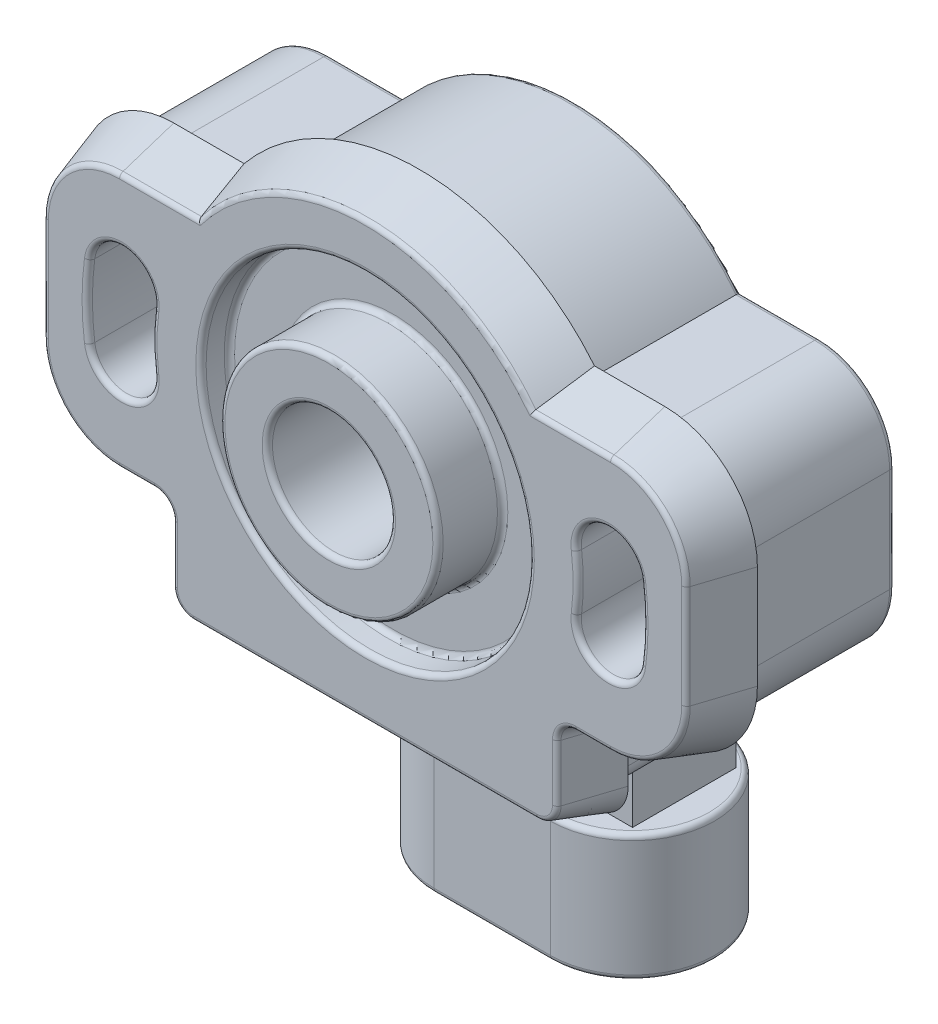
SolidWorks part; units mm, degrees
material "PVC Rigid"
ref_plane "Front Plane" through (0, 0, 0) normal (0, 0, 1) x (1, 0, 0)
ref_plane "Top Plane" through (0, 0, 0) normal (0, 1, 0) x (1, 0, 0)
ref_plane "Right Plane" through (0, 0, 0) normal (1, 0, 0) x (0, 0, -1)
sketch "Sketch3" plane through (0, 0, 0) normal (0, 0, 1) x (1, 0, 0)
  line L0 (12.8996, 9.8) -> (19, 9.8)
  line L1 (-19, -9.8) -> (-16.3, -9.8)
  line L2 (-24.8, -4) -> (-24.8, 4)
  line L3 (-19, 9.8) -> (-12.8996, 9.8)
  line L4 (24.8, -4) -> (24.8, 4)
  line L5 (-14.8, -11.3) -> (-14.8, -15.7)
  line L6 (-24.8, -9.8) -> (24.8, -9.8) construction
  line L7 (-24.8, -9.8) -> (-24.8, 9.8) construction
  line L8 (-24.8, 9.8) -> (24.8, 9.8) construction
  line L9 (24.8, -9.8) -> (24.8, 9.8) construction
  line L10 (0, 9.8) -> (0, -9.8) construction
  line L11 (-24.8, 0) -> (24.8, 0) construction
  line L12 (-13.3, -17.2) -> (13.3, -17.2)
  line L13 (14.8, -15.7) -> (14.8, -11.3)
  line L14 (16.3, -9.8) -> (19, -9.8)
  arc A0 (-24.8, -4) -> (-19, -9.8) centre (-19, -4) ccw
  arc A1 (19, -9.8) -> (24.8, -4) centre (19, -4) ccw
  arc A2 (19, 9.8) -> (24.8, 4) centre (19, 4) cw
  arc A3 (-24.8, 4) -> (-19, 9.8) centre (-19, 4) cw
  arc A4 (-12.8996, 9.8) -> (12.8996, 9.8) centre (0, 0) cw
  arc A5 (14.8, -11.3) -> (16.3, -9.8) centre (16.3, -11.3) cw
  arc A6 (13.3, -17.2) -> (14.8, -15.7) centre (13.3, -15.7) ccw
  arc A7 (-14.8, -15.7) -> (-13.3, -17.2) centre (-13.3, -15.7) ccw
  arc A8 (-14.8, -11.3) -> (-16.3, -9.8) centre (-16.3, -11.3) ccw
  point P0 (0, 0)
  point P28 (14.8, -9.8)
  point P31 (14.8, -17.2)
  point P34 (-14.8, -17.2)
  dimension "D3" = 49.6
  dimension "D4" = 16.2
  dimension "D5" = 29.6
  dimension "D6" = 7.4
  dimension "D1" = 5.8
  dimension "D2" = 19.6
  dimension "D7" = 1.5
extrude "Body" add sketch "Sketch3" along normal blind 16.2 contours A4 L0 A2 L4 A1 L14 A5 L13 A6 L12 A7 L5 A8 L1 A0 L2 A3 L3
ref_plane "Plane2" through (0, -15.7, 0) normal (0, 1, 0) x (1, 0, 0)
sketch "Sketch11" plane through (0, 0, 16.2) normal (0, 0, 1) x (1, 0, 0)
  line L0 (-19, 9.8) -> (-12.8996, 9.8) construction
  line L1 (-24.8, -4) -> (-24.8, 4) construction
  line L2 (-19, -9.8) -> (-16.3, -9.8) construction
  line L3 (-14.8, -11.3) -> (-14.8, -15.7) construction
  line L4 (-13.3, -17.2) -> (13.3, -17.2) construction
  line L5 (14.8, -15.7) -> (14.8, -11.3) construction
  line L6 (16.3, -9.8) -> (19, -9.8) construction
  line L7 (24.8, -4) -> (24.8, 4) construction
  line L8 (12.8996, 9.8) -> (19, 9.8) construction
  line L9 (-19, 9.8) -> (-12.8996, 9.8)
  line L10 (-24.8, -4) -> (-24.8, 4)
  line L11 (-19, -9.8) -> (-16.3, -9.8)
  line L12 (-14.8, -11.3) -> (-14.8, -15.7)
  line L13 (-13.3, -17.2) -> (13.3, -17.2)
  line L14 (14.8, -15.7) -> (14.8, -11.3)
  line L15 (16.3, -9.8) -> (19, -9.8)
  line L16 (24.8, -4) -> (24.8, 4)
  line L17 (12.8996, 9.8) -> (19, 9.8)
  arc A0 (-19, 9.8) -> (-24.8, 4) centre (-19, 4) ccw construction
  arc A1 (-24.8, -4) -> (-19, -9.8) centre (-19, -4) ccw construction
  arc A2 (-14.8, -11.3) -> (-16.3, -9.8) centre (-16.3, -11.3) ccw construction
  arc A3 (-14.8, -15.7) -> (-13.3, -17.2) centre (-13.3, -15.7) ccw construction
  arc A4 (13.3, -17.2) -> (14.8, -15.7) centre (13.3, -15.7) ccw construction
  arc A5 (16.3, -9.8) -> (14.8, -11.3) centre (16.3, -11.3) ccw construction
  arc A6 (19, -9.8) -> (24.8, -4) centre (19, -4) ccw construction
  arc A7 (24.8, 4) -> (19, 9.8) centre (19, 4) ccw construction
  arc A8 (12.8996, 9.8) -> (-12.8996, 9.8) centre (0, 0) ccw construction
  arc A9 (-19, 9.8) -> (-24.8, 4) centre (-19, 4) ccw
  arc A10 (-24.8, -4) -> (-19, -9.8) centre (-19, -4) ccw
  arc A11 (-14.8, -11.3) -> (-16.3, -9.8) centre (-16.3, -11.3) ccw
  arc A12 (-14.8, -15.7) -> (-13.3, -17.2) centre (-13.3, -15.7) ccw
  arc A13 (13.3, -17.2) -> (14.8, -15.7) centre (13.3, -15.7) ccw
  arc A14 (16.3, -9.8) -> (14.8, -11.3) centre (16.3, -11.3) ccw
  arc A15 (19, -9.8) -> (24.8, -4) centre (19, -4) ccw
  arc A16 (24.8, 4) -> (19, 9.8) centre (19, 4) ccw
  arc A17 (12.8996, 9.8) -> (-12.8996, 9.8) centre (0, 0) ccw
extrude "Lid Draft" add sketch "Sketch11" against normal blind 4.2 draft 18 draft outward yes
sketch "Sketch4" plane through (0, 0, 16.2) normal (0, 0, 1) x (1, 0, 0)
  circle A0 centre (0, 0) radius 12.7
  dimension "D1" = 12.7
extrude "Cut-Extrude1" cut sketch "Sketch4" against normal blind 2.2 contours A0
sketch "Sketch5" plane through (0, 0, 14) normal (0, 0, 1) x (1, 0, 0)
  circle A0 centre (0, 0) radius 8.45
  dimension "D1" = 8.45
extrude "Boss-Extrude2" add sketch "Sketch5" along normal blind 5
sketch "Sketch6" plane through (0, 0, 19) normal (0, 0, 1) x (1, 0, 0)
  circle A0 centre (0, 0) radius 4.7625
  dimension "D1" = 4.7625
extrude "3/8 Hole" cut sketch "Sketch6" against normal blind 16.6 contours A0
sketch "Sketch7" plane through (0, 0, 2.4) normal (0, 0, 1) x (1, 0, 0)
  line L0 (-2.3812, -4.1244) -> (2.3812, 4.1244) construction
  line L1 (0.7192, 2.7457) -> (2.0183, 1.9957)
  line L2 (2.0183, 1.9957) -> (3.0011, 3.698)
  line L3 (0.7192, 2.7457) -> (1.702, 4.448)
  circle A0 centre (0, 0) radius 4.7625 construction
  arc A1 (3.0011, 3.698) -> (1.702, 4.448) centre (0, 0) ccw
  circle A3 centre (0, 0) radius 4.7625 construction
  point P9 (0, 0)
  point P11 (1.3688, 2.3707)
  dimension "D1" = 1.5
  dimension "D2" = 7.5
extrude "Key" add sketch "Sketch7" along normal blind 12.8 contours L2 A1 L3 L1
sketch "Sketch12" plane through (0, 0, 16.2) normal (0, 0, 1) x (1, 0, 0)
  line L0 (-24.8, 0) -> (24.8, 0) construction
  line L1 (24.8, -4) -> (24.8, 4) construction
  line L2 (0, -17.2) -> (0, 16.2) construction
  line L3 (-13.3, -17.2) -> (13.3, -17.2) construction
  arc A0 (18.8375, -2.48) -> (18.8375, 2.48) centre (0, 0) ccw construction
  arc A1 (21.3161, -2.8063) -> (21.3161, 2.8063) centre (0, 0) ccw
  arc A2 (16.3588, -2.1537) -> (16.3588, 2.1537) centre (0, 0) ccw
  arc A3 (16.3588, -2.1537) -> (21.3161, -2.8063) centre (18.8375, -2.48) ccw
  arc A4 (21.3161, 2.8063) -> (16.3588, 2.1537) centre (18.8375, 2.48) ccw
  arc A5 (12.8996, 9.8) -> (-12.8996, 9.8) centre (0, 0) ccw construction
  arc A6 (-18.8375, -2.48) -> (-18.8375, 2.48) centre (0, 0) cw construction
  arc A7 (-21.3161, -2.8063) -> (-21.3161, 2.8063) centre (0, 0) cw
  arc A8 (-16.3588, -2.1537) -> (-16.3588, 2.1537) centre (0, 0) cw
  arc A9 (-16.3588, -2.1537) -> (-21.3161, -2.8063) centre (-18.8375, -2.48) cw
  arc A10 (-21.3161, 2.8063) -> (-16.3588, 2.1537) centre (-18.8375, 2.48) cw
  point P4 (19, 0)
  point P15 (0, 0)
  point P25 (-19, 0)
extrude "Cut-Extrude3" cut sketch "Sketch12" against normal through all
sketch "Sketch13" plane through (0, -15.7, 0) normal (0, 1, 0) x (1, 0, 0)
  line L1 (8.5, -4) -> (-8.5, -4)
  line L2 (8.5, -4) -> (8.5, 4)
  line L3 (8.5, 4) -> (-8.5, 4)
  line L4 (-8.5, -4) -> (-8.5, 4)
  line L5 (0, 4) -> (0, -4) construction
  line L6 (8.5, 0) -> (-8.5, 0) construction
  point P0 (0, 0)
  dimension "D1" = 8
  dimension "D2" = 17
extrude "Boss-Extrude5" add sketch "Sketch13" against normal blind 20.4
sketch "Sketch14" plane through (0, -36.1, 0) normal (0, -1, 0) x (1, 0, 0)
  line L0 (4.5, 0) -> (-4.5, 0) construction
  line L1 (10.85, 0) -> (-10.85, 0) construction
  line L2 (4.5, -6.35) -> (-4.5, -6.35)
  line L3 (4.5, 6.35) -> (-4.5, 6.35)
  arc A0 (4.5, -6.35) -> (4.5, 6.35) centre (4.5, 0) ccw
  arc A1 (-4.5, 6.35) -> (-4.5, -6.35) centre (-4.5, 0) ccw
  point P5 (0, 0)
  dimension "D1" = 12.7
  dimension "D2" = 21.7
extrude "Boss-Extrude6" add sketch "Sketch14" against normal blind 9.8
sketch "Sketch15" plane through (0, -36.1, 0) normal (0, -1, 0) x (1, 0, 0)
  line L4 (4.5, 4.85) -> (-4.5, 4.85)
  line L5 (-4.5, -4.85) -> (4.5, -4.85)
  line L6 (4.5, 4.85) -> (-4.5, 4.85)
  line L7 (-4.5, -4.85) -> (4.5, -4.85)
  arc A4 (4.5, -4.85) -> (4.5, 4.85) centre (4.5, 0) ccw
  arc A5 (-4.5, 4.85) -> (-4.5, -4.85) centre (-4.5, 0) ccw
  arc A6 (4.5, -4.85) -> (4.5, 4.85) centre (4.5, 0) ccw
  arc A7 (-4.5, 4.85) -> (-4.5, -4.85) centre (-4.5, 0) ccw
  dimension "D1" = 1.5
extrude "Cut-Extrude4" cut sketch "Sketch15" against normal blind 8.2
sketch "Sketch16" plane through (-8.5, 0, 0) normal (-1, 0, 0) x (0, 0, 1)
  line L0 (-4, -15.7) -> (-4, 2.1)
  line L1 (0, -15.7) -> (0, 8.7)
  line L2 (0, 8.7) -> (-4, 2.1)
  line L9 (-4, -15.7) -> (-4, -26.3)
  line L10 (-4, -26.3) -> (4, -26.3)
  line L11 (4, -26.3) -> (4, -17.2)
  line L12 (4, -17.2) -> (0, -17.2)
  line L13 (0, -17.2) -> (0, -15.7)
  line L14 (0, -15.7) -> (-4, -15.7)
  line L20 (0, -15.7) -> (-4, -15.7)
  dimension "D1" = 17.8
  dimension "D2" = 24.4
  dimension "D3" = 0
extrude "Boss-Extrude7" add sketch "Sketch16" against normal blind 0.8
sketch "Sketch17" plane through (8.5, 0, 0) normal (1, 0, 0) x (0, 0, -1)
  line L4 (0, -15.7) -> (4, -15.7)
  line L5 (4, -15.7) -> (4, 2.1)
  line L6 (4, 2.1) -> (0, 8.7)
  line L7 (0, 8.7) -> (0, -15.7)
  line L8 (0, -15.7) -> (4, -15.7)
  line L9 (4, -15.7) -> (4, 2.1)
  line L10 (4, 2.1) -> (0, 8.7)
  line L11 (0, 8.7) -> (0, -15.7)
  dimension "D1" = 0
extrude "Boss-Extrude8" add sketch "Sketch17" against normal blind 0.8
ref_plane "Plane3" through (0, 0, 0) normal (-1, 0, 0) x (0, 0, 1)
sketch "Sketch18" plane through (0, 0, 0) normal (-1, 0, 0) x (0, 0, 1)
  line L0 (-4, -15.7) -> (0, -15.7) construction
  line L1 (-4, -15.7) -> (0, -15.7)
  line L2 (0, -15.7) -> (0, -6)
  line L3 (0, -15.7) -> (-2.8, -15.7)
  line L4 (-2.8, -15.7) -> (-2.8, -10.7)
  line L5 (-2.8, -10.7) -> (0, -6)
  dimension "D1" = 9.7
  dimension "D2" = 2.8
  dimension "D3" = 5
extrude "Boss-Extrude9" add sketch "Sketch18" along normal blind 0.4 and the other way blind 0.4 contours L3 L4 L5 L2
fillet "Fillet2" radius 0.4 70 edges at (0, -26.3, 6.35) (10.85, -26.3, 0) (0, -26.3, -6.35) (-21.5, 0, 0) (-18.5111, 4.9586, 0) (-16.5, 0, 0) (16.5, 0, 0) (18.5111, 4.9586, 0) (21.5, 0, 0) (10.9, -17.2, 0) (14.3607, -16.7607, 0) (15.9498, 9.8, 0) (23.1012, 8.1012, 0) (24.8, 0, 0) (23.1012, -8.1012, 0) (17.65, -9.8, 0) (15.2393, -10.2393, 0) (-10.9, -17.2, 0) (-14.3607, -16.7607, 0) (-14.8, -13.5, 0) (-15.2393, -10.2393, 0) (-17.65, -9.8, 0) (-23.1012, -8.1012, 0) (-24.8, 0, 0) (-23.1012, 8.1012, 0) (0, -36.1, -6.35) (-10.85, -36.1, 0) (0, -36.1, 6.35) (10.85, -36.1, 0) (-9.35, -36.1, 0) (0, -36.1, -4.85) (9.35, -36.1, 0) (0, -36.1, 4.85) (8.45, 0, 19) (4.7625, 0, 19) (12.7, 0, 14) (8.45, 0, 14) (-18.5111, 4.9586, 16.2) (-21.5, 0, 16.2) (-18.5111, -4.9586, 16.2) (-16.5, 0, 16.2) (0, 16.2, 16.2) (15.9498, 9.8, 16.2) (23.1012, 8.1012, 16.2) (24.8, 0, 16.2) (23.1012, -8.1012, 16.2) (17.65, -9.8, 16.2) (15.2393, -10.2393, 16.2) (14.8, -13.5, 16.2) (14.3607, -16.7607, 16.2) (0, -17.2, 16.2) (-14.3607, -16.7607, 16.2) (-14.8, -13.5, 16.2) (-15.2393, -10.2393, 16.2) (-17.65, -9.8, 16.2) (-23.1012, -8.1012, 16.2) (-24.8, 0, 16.2) (-23.1012, 8.1012, 16.2) (-15.9498, 9.8, 16.2) (12.7, 0, 16.2) (18.5111, 4.9586, 16.2) (16.5, 0, 16.2) (18.5111, -4.9586, 16.2) (21.5, 0, 16.2) (-10.85, -26.3, 0) (-18.5111, -4.9586, 0) (18.5111, -4.9586, 0) (14.8, -13.5, 0) (-15.9498, 9.8, 0) (0, 16.2, 0)
ref_axis "Axis1" through (0, 0, 2.4) along (0, 0, 1)
sketch3d "3DSketch1"
  line L0 (19, 0, 16.2) -> (-19, 0, 16.2) construction
  line L1 (0, 0, 2.4) -> (0, 0, 18.6) construction
  point P2 (0, 0, 16.2)
  point P9 (0, 0, 16.2)
  dimension "D1" = 38
